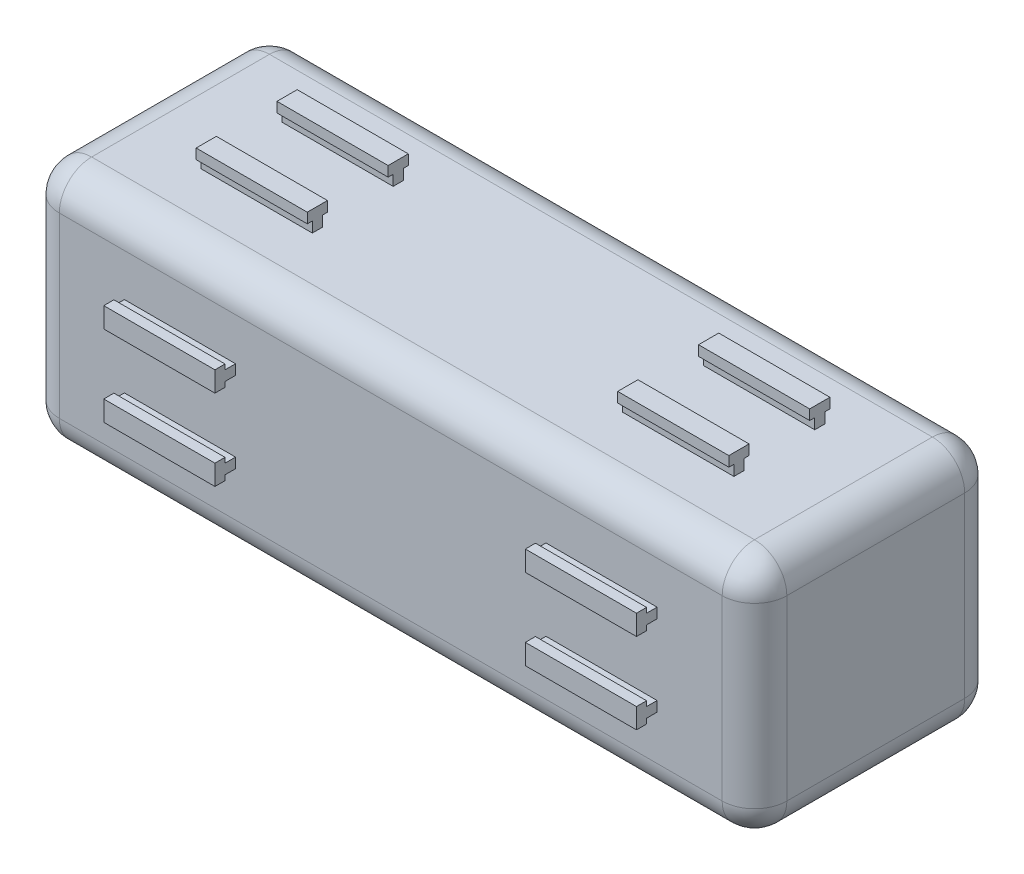
SolidWorks part; units mm, degrees
ref_plane "Front Plane" through (0, 0, 0) normal (0, 0, 1) x (1, 0, 0)
ref_plane "Top Plane" through (0, 0, 0) normal (0, 1, 0) x (1, 0, 0)
ref_plane "Right Plane" through (0, 0, 0) normal (1, 0, 0) x (0, 0, -1)
sketch "Sketch1" plane through (0, 0, 0) normal (0, 1, 0) x (1, 0, 0)
  line L1 (-90, -30) -> (90, -30)
  line L2 (-90, -30) -> (-90, 30)
  line L3 (-90, 30) -> (90, 30)
  line L4 (90, -30) -> (90, 30)
  line L5 (-90, -30) -> (90, 30) construction
  line L6 (-90, 30) -> (90, -30) construction
  point P0 (0, 0)
  dimension "D1" = 180
  dimension "D2" = 60
ref_plane "Plane1" through (52.15, 0, 0) normal (1, 0, 0) x (0, 0, -1)
sketch "Sketch3" plane through (52.15, 0, 0) normal (1, 0, 0) x (0, 0, -1)
  line L0 (-11, 0) -> (-11, 2.6)
  line L1 (-11, 2.6) -> (-12.25, 2.6)
  line L2 (-12.25, 2.6) -> (-12.25, 5.1)
  line L3 (-12.25, 5.1) -> (-7.25, 5.1)
  line L4 (-7.25, 5.1) -> (-7.25, 2.6)
  line L5 (-7.25, 2.6) -> (-8.5, 2.6)
  line L6 (-8.5, 2.6) -> (-8.5, 0)
  line L7 (-8.5, 0) -> (-11, 0)
  line L8 (-9.75, -37.9156) -> (-9.75, 37.9156) construction
  line L9 (0.25, -37.9156) -> (0.25, 37.9156) construction
  line L10 (9, 0) -> (11.5, 0)
  line L11 (9, 2.6) -> (9, 0)
  line L12 (7.75, 2.6) -> (9, 2.6)
  line L13 (7.75, 5.1) -> (7.75, 2.6)
  line L14 (12.75, 5.1) -> (7.75, 5.1)
  line L15 (12.75, 2.6) -> (12.75, 5.1)
  line L16 (11.5, 2.6) -> (12.75, 2.6)
  line L17 (11.5, 0) -> (11.5, 2.6)
  line L18 (-30, 0) -> (30, 0) construction
  dimension "D1" = 7.5
extrude "Boss-Extrude1" add sketch "Sketch3" along normal mid plane 27.5
extrude "Boss-Extrude2" add sketch "Sketch1" against normal blind 60
fillet "Fillet2" radius 8 12 edges at (-90, -60, 0) (-90, 0, 0) (-90, -30, -30) (0, -60, -30) (0, 0, -30) (90, -30, -30) (90, -60, 0) (90, 0, 0) (90, -30, 30) (0, -60, 30) (-90, -30, 30) (0, 0, 30)
sketch3d "3DSketch3"
  line L0 (90, -8, 0) -> (90, -52, 0)
  line L1 (90, -8, -22) -> (90, -8, 22) construction
  line L2 (90, -52, 22) -> (90, -52, -22) construction
  point P6 (90, -30, 0)
  point P7 (90, -30, 0)
ref_axis "Axis2" through (90, -30, 0) along (1, 0, 0)
pattern_circular "CirPattern1" count 4 over 360 about axis through (90, -30, 0) along (1, 0, 0) of "Boss-Extrude1"
mirror "Mirror6" about plane through (0, 0, 0) normal (1, 0, 0) of "CirPattern1"
